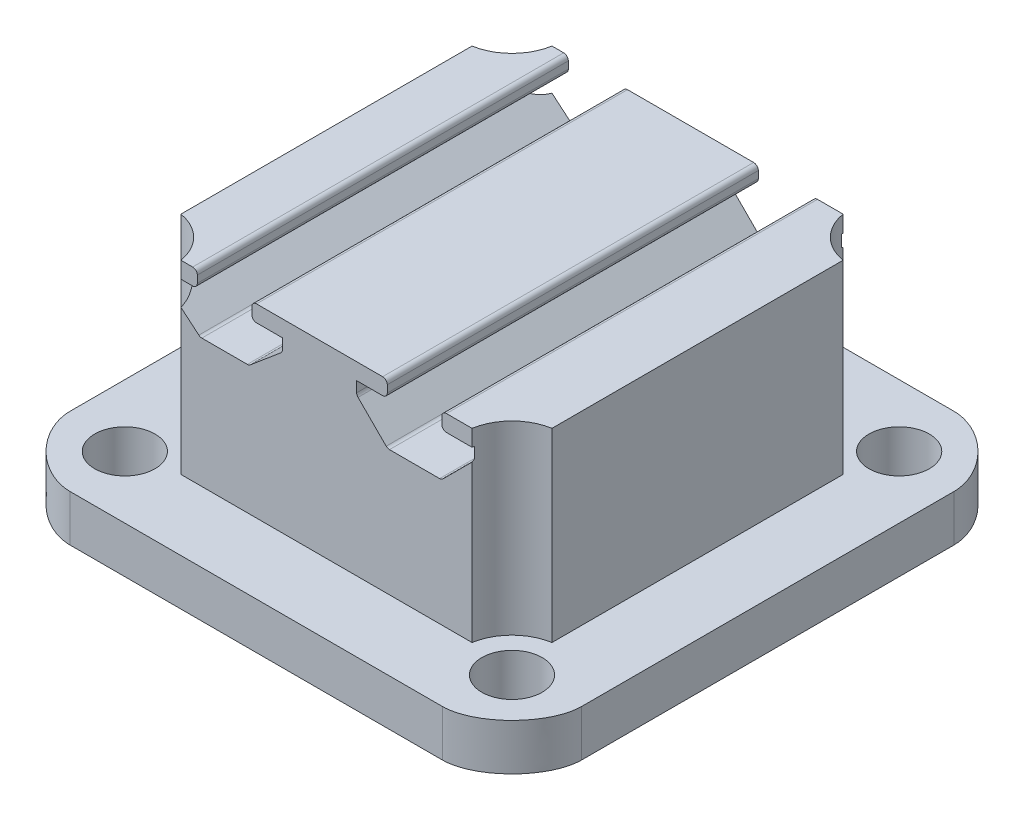
SolidWorks part; units mm, degrees
ref_plane "Front Plane" through (0, 0, 0) normal (0, 0, 1) x (1, 0, 0)
ref_plane "Top Plane" through (0, 0, 0) normal (0, 1, 0) x (1, 0, 0)
ref_plane "Right Plane" through (0, 0, 0) normal (1, 0, 0) x (0, 0, -1)
sketch "Sketch1" plane through (0, 0, 0) normal (0, 1, 0) x (1, 0, 0)
  line L1 (-27.57, -27.57) -> (27.57, -27.57)
  line L2 (-27.57, -27.57) -> (-27.57, 27.57)
  line L3 (-27.57, 27.57) -> (27.57, 27.57)
  line L4 (27.57, -27.57) -> (27.57, 27.57)
  line L5 (-27.57, -27.57) -> (27.57, 27.57) construction
  line L6 (-27.57, 27.57) -> (27.57, -27.57) construction
  point P0 (0, 0)
  dimension "D1" = 55.14
  dimension "D2" = 55.14
extrude "Boss-Extrude1" add sketch "Sketch1" along normal blind 5
sketch "Sketch2" plane through (0, 5, 0) normal (0, 1, 0) x (1, 0, 0)
  line L0 (-27.57, -27.57) -> (27.57, -27.57) construction
  line L1 (27.57, -27.57) -> (27.57, 27.57) construction
  line L2 (-27.57, 27.57) -> (-27.57, -27.57) construction
  line L3 (27.57, 27.57) -> (-27.57, 27.57) construction
  circle A0 centre (20.87, -20.87) radius 3.25
  circle A1 centre (-20.87, -20.87) radius 3.25
  circle A2 centre (-20.87, 20.87) radius 3.25
  circle A3 centre (20.87, 20.87) radius 3.25
  dimension "D2" = 6.5
  dimension "D3" = 6.7
  dimension "D4" = 6.5
  dimension "D5" = 6.7
  dimension "D7" = 6.5
  dimension "D10" = 6.5
  dimension "D12" = 6.7
  dimension "D1" = 6.7
  dimension "D6" = 6.7
  dimension "D8" = 6.7
  dimension "D9" = 6.7
  dimension "D11" = 6.7
extrude "Cut-Extrude1" cut sketch "Sketch2" against normal through all
fillet "Fillet1" radius 7.5 4 edges at (-27.57, 2.5, -27.57) (-27.57, 2.5, 27.57) (27.57, 2.5, 27.57) (27.57, 2.5, -27.57) conic radius 10
sketch "Sketch3" plane through (0, 5, 0) normal (0, 1, 0) x (1, 0, 0)
  line L1 (-20, -20) -> (20, -20)
  line L2 (-20, -20) -> (-20, 20)
  line L3 (-20, 20) -> (20, 20)
  line L4 (20, -20) -> (20, 20)
  line L5 (-20, -20) -> (20, 20) construction
  line L6 (-20, 20) -> (20, -20) construction
  point P0 (0, 0)
  dimension "D1" = 40
  dimension "D2" = 40
extrude "Boss-Extrude2" add sketch "Sketch3" along normal blind 20
extrude "Cut-Extrude2" cut sketch "Sketch2<2>" against normal through all both and the other way through all
sketch "Sketch2<2>" plane through (0, 5, 0) normal (0, 1, 0) x (1, 0, 0) same geometry as "Sketch2"
sketch "Sketch5" plane through (0, 5, 0) normal (0, 1, 0) x (1, 0, 0)
  circle A0 centre (-20.87, 20.87) radius 5.25
  arc A1 (-17.7386, 20) -> (-20, 17.7386) centre (-20.87, 20.87) ccw construction
  circle A2 centre (20.87, 20.87) radius 5.25
  arc A3 (20, 17.7386) -> (17.7386, 20) centre (20.87, 20.87) ccw construction
  circle A4 centre (-20.87, -20.87) radius 5.25
  arc A5 (-20, -17.7386) -> (-17.7386, -20) centre (-20.87, -20.87) ccw construction
  circle A6 centre (20.87, -20.87) radius 5.25
  arc A7 (17.7386, -20) -> (20, -17.7386) centre (20.87, -20.87) ccw construction
  dimension "D1" = 2
  dimension "D2" = 2
  dimension "D3" = 2
  dimension "D4" = 2
extrude "Cut-Extrude3" cut sketch "Sketch5" along normal blind 20
sketch "Sketch8" plane through (0, 0, 20) normal (0, 0, 1) x (1, 0, 0)
  line L0 (-13.9258, 25) -> (-13.9258, 23.23)
  line L1 (-13.9258, 23.23) -> (-17.2258, 23.23)
  line L2 (-17.2258, 23.23) -> (-17.2258, 21.89)
  line L3 (-17.2258, 21.89) -> (-13.6208, 18.8588)
  line L4 (-13.6208, 18.8588) -> (-8.3508, 18.8588)
  line L5 (-8.3508, 18.8588) -> (-4.7458, 21.89)
  line L6 (-4.7458, 21.89) -> (-4.7458, 23.23)
  line L7 (-4.7458, 23.23) -> (-8.0458, 23.23)
  line L8 (-8.0458, 23.23) -> (-8.0458, 25)
  line L9 (-8.0458, 25) -> (-13.9258, 25)
  line L10 (6.5542, 25) -> (6.5542, 23.23)
  line L11 (6.5542, 23.23) -> (3.2542, 23.23)
  line L12 (3.2542, 23.23) -> (3.2542, 21.89)
  line L13 (3.2542, 21.89) -> (6.5847, 18.5595)
  line L14 (6.5847, 18.5595) -> (12.4037, 18.5595)
  line L15 (12.4037, 18.5595) -> (15.7342, 21.89)
  line L16 (15.7342, 21.89) -> (15.7342, 23.23)
  line L17 (15.7342, 23.23) -> (12.4342, 23.23)
  line L18 (12.4342, 23.23) -> (12.4342, 25)
  line L19 (12.4342, 25) -> (6.5542, 25)
  line L20 (-15.6926, 25) -> (15.6926, 25) construction
  dimension "D1" = 0
  dimension "D2" = 0
extrude "Cut-Extrude5" cut sketch "Sketch8" against normal through all
fillet "Fillet5" radius 0.5 16 edges at (15.7342, 21.89, 0) (3.2542, 21.89, 0) (12.4037, 18.5595, 0) (6.5847, 18.5595, 0) (6.5542, 25, 0) (6.5542, 23.23, 0) (12.4342, 23.23, 0) (12.4342, 25, 0) (-8.0458, 25, 0) (-8.0458, 23.23, 0) (-4.7458, 21.89, 0) (-8.3508, 18.8588, 0) (-13.6208, 18.8588, 0) (-17.2258, 21.89, 0) (-13.9258, 23.23, 0) (-13.9258, 25, 0)
